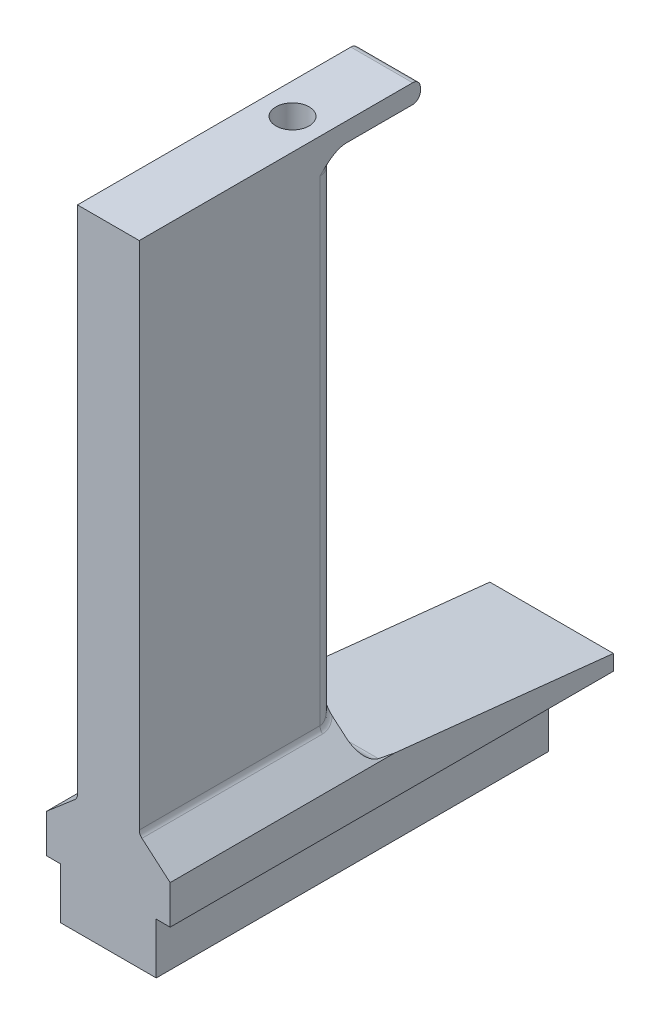
SolidWorks part; units mm, degrees
ref_plane "Front Plane" through (0, 0, 0) normal (0, 0, 1) x (1, 0, 0)
ref_plane "Top Plane" through (0, 0, 0) normal (0, 1, 0) x (1, 0, 0)
ref_plane "Right Plane" through (0, 0, 0) normal (1, 0, 0) x (0, 0, -1)
sketch "Sketch1" plane through (0, 0, 0) normal (0, 1, 0) x (1, 0, 0)
  line L1 (-6.2, 25.4) -> (6.2, 25.4)
  line L2 (-6.2, 25.4) -> (-6.2, -25.4)
  line L3 (-6.2, -25.4) -> (6.2, -25.4)
  line L4 (6.2, 25.4) -> (6.2, -25.4)
  line L5 (-6.2, 25.4) -> (6.2, -25.4) construction
  line L6 (-6.2, -25.4) -> (6.2, 25.4) construction
  point P0 (0, 0)
  dimension "D1" = 12.4
  dimension "D2" = 50.8
extrude "Boss-Extrude1" add sketch "Sketch1" along normal blind 6.6
sketch "Sketch2" plane through (0, 6.6, 0) normal (0, 1, 0) x (1, 0, 0)
  line L0 (-6.2, -25.4) -> (-8, -25.4)
  line L1 (-8, 32) -> (8, 32)
  line L2 (-8, 32) -> (-8, -32)
  line L3 (-8, -32) -> (8, -32)
  line L4 (8, 32) -> (8, -32)
  line L5 (-8, 32) -> (8, -32) construction
  line L6 (-8, -32) -> (8, 32) construction
  line L7 (-8, -25.4) -> (8, -25.4)
  point P0 (0, 0)
  line M3 (6.2, -25.4) -> (6.2, 25.4)
  line M4 (6.2, 25.4) -> (-6.2, 25.4)
  line M5 (-6.2, 25.4) -> (-6.2, -25.4)
  line M6 (-6.2, -25.4) -> (6.2, -25.4)
  dimension "D1" = 16
  dimension "D2" = 64
extrude "Boss-Extrude2" add sketch "Sketch2" along normal blind 75 contours L7 L4 L1 L2 L0 M3 M5 M4 | M6 M3 M4 M5 region at (0, 6.6, 0) region at (-7.1, 6.6, 24.8041)
sketch "Sketch3" plane through (-8, 0, 0) normal (-1, 0, 0) x (0, 0, 1)
  line L0 (-32, 6.6) -> (-32, 8.6)
  line L1 (-32, 81.6) -> (-32, 6.6) construction
  line L2 (-32, 8.6) -> (0, 11.9845)
  line L3 (0, 11.9845) -> (0, 79.1369)
  line L4 (0, 79.1369) -> (-11.0013, 79.1369)
  line L5 (-11.0013, 79.1369) -> (-11.0013, 81.6)
  line L6 (-32, 81.6) -> (25.4, 81.6) construction
  line L7 (-11.0013, 81.6) -> (-17.7988, 88.3975)
  line L8 (-17.7988, 88.3975) -> (-38.422, 89.438)
  line L9 (-38.422, 89.438) -> (-42.5005, 8.6)
  line L10 (-42.5005, 8.6) -> (-32, 6.6)
  dimension "D1" = 2
extrude "Cut-Extrude1" cut sketch "Sketch3" against normal blind 75
sketch "Sketch4" plane through (0, 0, 25.4) normal (0, 0, 1) x (1, 0, 0)
  line L0 (-8, 6.6) -> (-8, 11.6)
  line L1 (-8, 81.6) -> (-8, 6.6) construction
  line L2 (8, 6.6) -> (8, 11.6)
  line L3 (8, 81.6) -> (8, 6.6) construction
  line L4 (0, 81.6) -> (0, 72.5511)
  line L5 (-8, 81.6) -> (8, 81.6) construction
  line L6 (0, 81.6) -> (-4, 81.6)
  line L7 (0, 81.6) -> (4, 81.6)
  line L8 (-4, 81.6) -> (-4, 6.0718)
  line L9 (4, 81.6) -> (4, 6.0718)
  line L10 (-8, 11.6) -> (-4, 15.0372)
  line L11 (8, 11.6) -> (4, 15.0372)
  line L12 (8, 11.6) -> (21.8528, 45.261)
  line L13 (21.8528, 45.261) -> (27.1219, 107.0946)
  line L14 (27.1219, 107.0946) -> (-33.6246, 92.4643)
  line L15 (-33.6246, 92.4643) -> (-25.3081, 57.9334)
  line L16 (-25.3081, 57.9334) -> (-8, 11.6)
  line M9 (8, 6.6) -> (8, 81.6)
  line M10 (8, 81.6) -> (-8, 81.6)
  line M11 (-8, 81.6) -> (-8, 6.6)
  dimension "D1" = 5
  dimension "D2" = 5
  dimension "D3" = 4
  dimension "D4" = 4
  dimension "D5" = 5.2739
extrude "Cut-Extrude2" cut sketch "Sketch4" against normal blind 75 contours L10 L8 M11 M10 | L15 L16 L12 L13 L14 M11 M10 M9 | L11 L9 M9 M10 region at (-2, 82.7318, 25.4) region at (-6.0168, 47.4521, 25.4) region at (6.0168, 47.4521, 25.4)
fillet "Fillet1" radius 2 1 edges at (0, 11.9845, 0)
fillet "Fillet2" radius 2 2 edges at (4, 47.0871, 0) (-4, 47.0871, 0)
fillet "Fillet3" radius 2 3 edges at (3.4142, 79.1369, 0.5858) (-3.4142, 79.1369, 0.5858) (0, 79.1369, 0)
fillet "Fillet4" radius 1 2 edges at (0, 81.6, -11.0013) (0, 79.1369, -11.0013)
fillet "Fillet5" radius 1 4 edges at (3.4142, 15.5406, 0.5858) (-3.4142, 15.5406, 0.5858) (4, 15.0372, 13.7) (-4, 15.0372, 13.7)
sketch "Sketch5" plane through (0, 81.6, 0) normal (0, 1, 0) x (1, 0, 0)
  circle A0 centre (0, -1.5555) radius 2.15
  dimension "D1" = 4.3
extrude "Cut-Extrude3" cut sketch "Sketch5" against normal blind 75
